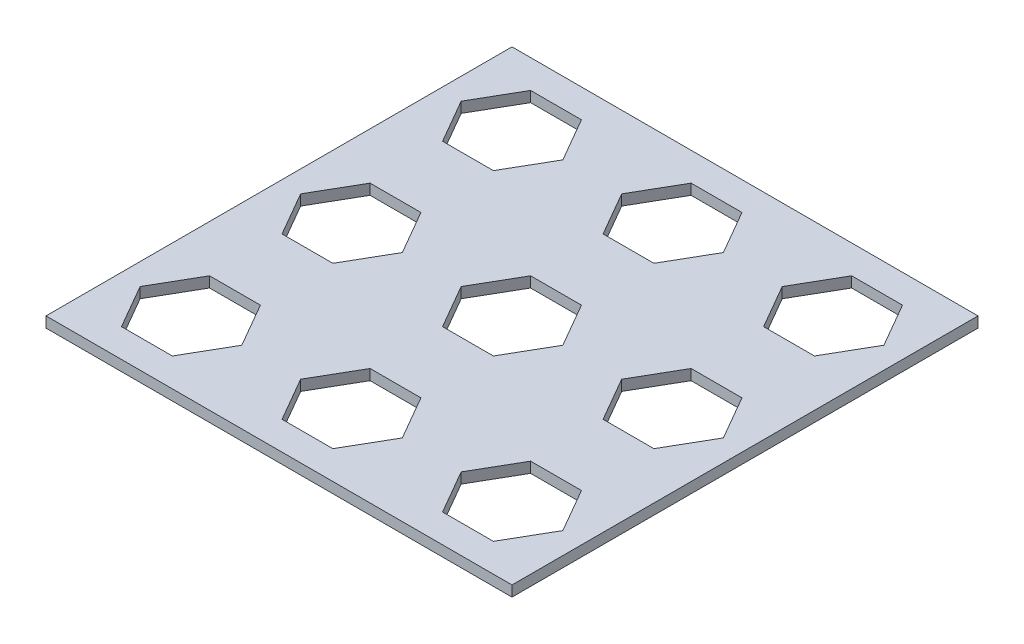
SolidWorks part; units mm, degrees
material "Commercially Pure titanium (Ti-55)  UNS R50550*"
ref_plane "Front Plane" through (0, 0, 0) normal (0, 0, 1) x (1, 0, 0)
ref_plane "Top Plane" through (0, 0, 0) normal (0, 1, 0) x (1, 0, 0)
ref_plane "Right Plane" through (0, 0, 0) normal (1, 0, 0) x (0, 0, -1)
sketch "Sketch1" plane through (0, 0, 0) normal (0, 1, 0) x (1, 0, 0)
  line L1 (-34.925, -34.925) -> (34.925, -34.925)
  line L2 (-34.925, -34.925) -> (-34.925, 34.925)
  line L3 (-34.925, 34.925) -> (34.925, 34.925)
  line L4 (34.925, -34.925) -> (34.925, 34.925)
  line L5 (-34.925, -34.925) -> (34.925, 34.925) construction
  line L6 (-34.925, 34.925) -> (34.925, -34.925) construction
  line L7 (-20.2516, 30.6607) -> (-27.8716, 30.6607)
  line L8 (-27.8716, 30.6607) -> (-31.6816, 24.0616)
  line L9 (-31.6816, 24.0616) -> (-27.8716, 17.4625)
  line L10 (-27.8716, 17.4625) -> (-20.2516, 17.4625)
  line L11 (-20.2516, 17.4625) -> (-16.4416, 24.0616)
  line L12 (-16.4416, 24.0616) -> (-20.2516, 30.6607)
  line L60 (-34.925, 0) -> (34.925, 0) construction
  line L61 (0, 34.925) -> (0, -34.925) construction
  line L62 (-34.925, -17.4625) -> (34.925, -17.4625) construction
  line L63 (-34.925, 17.4625) -> (34.925, 17.4625) construction
  line L65 (-3.81, 17.4625) -> (3.81, 17.4625)
  line L66 (3.81, 17.4625) -> (7.62, 24.0616)
  line L67 (7.62, 24.0616) -> (3.81, 30.6607)
  line L68 (3.81, 30.6607) -> (-3.81, 30.6607)
  line L69 (-3.81, 30.6607) -> (-7.62, 24.0616)
  line L70 (-7.62, 24.0616) -> (-3.81, 17.4625)
  line L88 (20.2516, -17.4625) -> (16.4416, -24.0616)
  line L89 (16.4416, 24.0616) -> (20.2516, 30.6607)
  line L90 (20.2516, 17.4625) -> (16.4416, 24.0616)
  line L91 (27.8716, 17.4625) -> (20.2516, 17.4625)
  line L92 (31.6816, 24.0616) -> (27.8716, 17.4625)
  line L93 (27.8716, 30.6607) -> (31.6816, 24.0616)
  line L94 (20.2516, 30.6607) -> (27.8716, 30.6607)
  line L95 (27.8716, -17.4625) -> (20.2516, -17.4625)
  line L96 (31.6816, -24.0616) -> (27.8716, -17.4625)
  line L97 (27.8716, -30.6607) -> (31.6816, -24.0616)
  line L98 (20.2516, -30.6607) -> (27.8716, -30.6607)
  line L99 (16.4416, -24.0616) -> (20.2516, -30.6607)
  line L100 (-7.62, -24.0616) -> (-3.81, -17.4625)
  line L101 (-3.81, -30.6607) -> (-7.62, -24.0616)
  line L102 (3.81, -30.6607) -> (-3.81, -30.6607)
  line L103 (7.62, -24.0616) -> (3.81, -30.6607)
  line L104 (3.81, -17.4625) -> (7.62, -24.0616)
  line L105 (-3.81, -17.4625) -> (3.81, -17.4625)
  line L106 (-16.4416, -24.0616) -> (-20.2516, -30.6607)
  line L107 (-20.2516, -17.4625) -> (-16.4416, -24.0616)
  line L108 (-27.8716, -17.4625) -> (-20.2516, -17.4625)
  line L109 (-31.6816, -24.0616) -> (-27.8716, -17.4625)
  line L110 (-27.8716, -30.6607) -> (-31.6816, -24.0616)
  line L111 (-20.2516, -30.6607) -> (-27.8716, -30.6607)
  line L112 (-34.925, 12.0308) -> (34.925, 12.0308) construction
  line L113 (20.2516, 6.5991) -> (16.4416, 0)
  line L114 (27.8716, 6.5991) -> (20.2516, 6.5991)
  line L115 (31.6816, 0) -> (27.8716, 6.5991)
  line L116 (27.8716, -6.5991) -> (31.6816, 0)
  line L117 (20.2516, -6.5991) -> (27.8716, -6.5991)
  line L118 (16.4416, 0) -> (20.2516, -6.5991)
  line L119 (-7.62, 0) -> (-3.81, 6.5991)
  line L120 (-3.81, -6.5991) -> (-7.62, 0)
  line L121 (3.81, -6.5991) -> (-3.81, -6.5991)
  line L122 (7.62, 0) -> (3.81, -6.5991)
  line L123 (3.81, 6.5991) -> (7.62, 0)
  line L124 (-3.81, 6.5991) -> (3.81, 6.5991)
  line L125 (-16.4416, 0) -> (-20.2516, -6.5991)
  line L126 (-20.2516, 6.5991) -> (-16.4416, 0)
  line L127 (-27.8716, 6.5991) -> (-20.2516, 6.5991)
  line L128 (-31.6816, 0) -> (-27.8716, 6.5991)
  line L129 (-27.8716, -6.5991) -> (-31.6816, 0)
  line L130 (-20.2516, -6.5991) -> (-27.8716, -6.5991)
  circle A0 centre (-24.0616, 24.0616) radius 6.5991 construction
  circle A1 centre (0, 24.0616) radius 6.5991 construction
  point P0 (0, 0)
  dimension "D1" = 69.85
  dimension "D2" = 69.85
extrude "Boss-Extrude1" add sketch "Sketch1" along normal blind 1.5875
